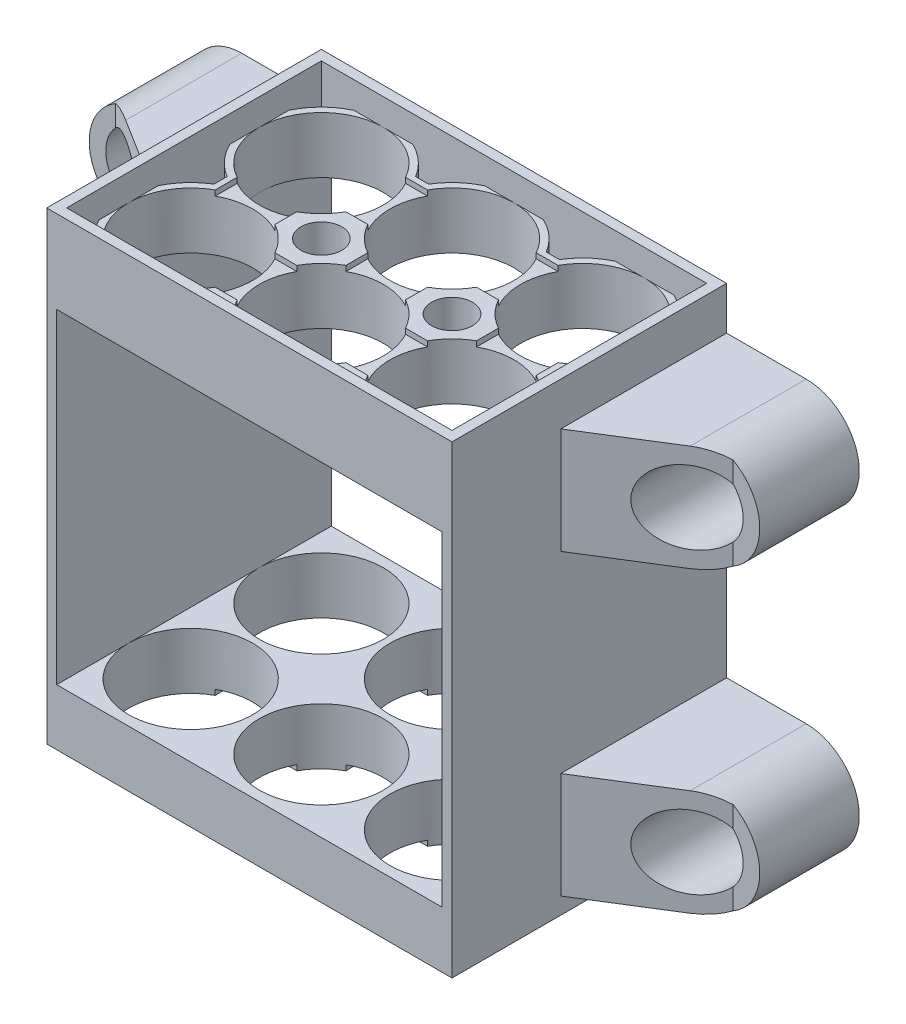
SolidWorks part; units mm, degrees
note: The reader was unsure of these and kept them because the rebuilt part matched: shared geometry of "Sketch5<3>", "Sketch12<3>".
ref_plane "Front Plane" through (0, 0, 0) normal (0, 0, 1) x (1, 0, 0)
ref_plane "Top Plane" through (0, 0, 0) normal (0, 1, 0) x (1, 0, 0)
ref_plane "Right Plane" through (0, 0, 0) normal (1, 0, 0) x (0, 0, -1)
sketch "Sketch3" plane through (0, 0, 0) normal (0, 1, 0) x (1, 0, 0)
  line L0 (-19.7, 9.85) -> (-10.35, 9.85) construction
  line L1 (-10.35, 9.85) -> (-9.35, 9.85) construction
  line L2 (-9.35, 9.85) -> (0, 9.85) construction
  line L3 (0, 9.85) -> (9.35, 9.85) construction
  line L4 (9.35, 9.85) -> (10.35, 9.85) construction
  line L5 (10.35, 9.85) -> (19.7, 9.85) construction
  line L6 (19.7, 9.85) -> (19.7, 0.5) construction
  line L7 (19.7, 0.5) -> (19.7, -0.5) construction
  line L8 (19.7, -0.5) -> (19.7, -9.85) construction
  line L9 (19.7, -9.85) -> (10.35, -9.85) construction
  line L10 (10.35, -9.85) -> (9.35, -9.85) construction
  line L11 (9.35, -9.85) -> (0, -9.85) construction
  line L12 (0, -9.85) -> (-9.35, -9.85) construction
  line L13 (-9.35, -9.85) -> (-10.35, -9.85) construction
  line L14 (-10.35, -9.85) -> (-19.7, -9.85) construction
  line L15 (-19.7, -9.85) -> (-19.7, -0.5) construction
  line L16 (-19.7, -0.5) -> (-19.7, 0.5) construction
  line L17 (-19.7, 0.5) -> (-19.7, 9.85) construction
  line L18 (0, 9.85) -> (0, 0.5) construction
  line L19 (0, 0.5) -> (0, -0.5) construction
  line L20 (0, -0.5) -> (0, -9.85) construction
  line L21 (0, 9.85) -> (0, 19.2) construction
  line L22 (-30.55, 20.7) -> (30.55, 20.7)
  line L23 (-30.55, 20.7) -> (-30.55, -20.7)
  line L24 (-30.55, -20.7) -> (30.55, -20.7)
  line L25 (30.55, 20.7) -> (30.55, -20.7)
  line L26 (0, 19.2) -> (0, 20.7) construction
  line L27 (-19.7, -9.85) -> (-29.05, -9.85) construction
  line L28 (-29.05, -9.85) -> (-30.55, -9.85) construction
  line L29 (-30.55, 20.7) -> (30.55, -20.7) construction
  circle A0 centre (-19.7, 9.85) radius 9.35
  circle A1 centre (0, 9.85) radius 9.35
  circle A2 centre (19.7, 9.85) radius 9.35
  circle A3 centre (-19.7, -9.85) radius 9.35
  circle A4 centre (0, -9.85) radius 9.35
  circle A5 centre (19.7, -9.85) radius 9.35
  dimension "D1" = 18.7
  dimension "D2" = 1
  dimension "D3" = 1
  dimension "D4" = 1
  dimension "D5" = 1.5
  dimension "D6" = 1.5
extrude "Boss-Extrude1" add sketch "Sketch3" along normal blind 66
sketch "Sketch4" plane through (0, 0, 0) normal (0, 1, 0) x (1, 0, 0)
  line L0 (-9.85, 0) -> (9.85, 0) construction
  line L1 (-19.7, -9.85) -> (0, 9.85) construction
  line L2 (-15.2615, 19.2) -> (-4.4385, 19.2)
  line L4 (-8.86, 15.2) -> (-10.84, 15.2)
  line L6 (-9.85, 19.2) -> (-9.85, 15.2) construction
  line L7 (-9.85, 0) -> (-9.85, 15.2) construction
  line L8 (-9.85, 19.2) -> (-9.85, 20.7) construction
  line L9 (30.55, 20.7) -> (-30.55, 20.7) construction
  line L10 (-9.85, 0) -> (-12.0279, 2.1779) construction
  line L11 (-12.0279, 2.1779) -> (-12.3814, 2.5314) construction
  line L12 (-12.3814, 2.5314) -> (-19.7, 9.85) construction
  line L13 (-4.4385, 19.2) -> (4.4385, 19.2) construction
  line L14 (4.4385, 19.2) -> (15.2615, 19.2)
  line L15 (15.2615, 19.2) -> (24.1385, 19.2) construction
  line L16 (24.1385, 19.2) -> (29.05, 19.2)
  line L17 (29.05, 19.2) -> (29.05, 14.2885)
  line L18 (29.05, 5.4115) -> (29.05, -5.4115)
  line L19 (29.05, -19.2) -> (29.05, -14.2885)
  line L20 (29.05, -19.2) -> (24.1385, -19.2)
  line L21 (24.1385, -19.2) -> (15.2615, -19.2) construction
  line L22 (15.2615, -19.2) -> (4.4385, -19.2)
  line L23 (4.4385, -19.2) -> (-4.4385, -19.2) construction
  line L24 (-4.4385, -19.2) -> (-15.2615, -19.2)
  line L25 (-15.2615, -19.2) -> (-24.1385, -19.2) construction
  line L26 (-24.1385, -19.2) -> (-29.05, -19.2)
  line L27 (-29.05, -19.2) -> (-29.05, -14.2885)
  line L28 (-29.05, -14.2885) -> (-29.05, -5.4115) construction
  line L29 (-29.05, -5.4115) -> (-29.05, 5.4115)
  line L30 (-29.05, 5.4115) -> (-29.05, 14.2885) construction
  line L31 (-29.05, 14.2885) -> (-29.05, 19.2)
  line L32 (-29.05, 19.2) -> (-24.1385, 19.2)
  line L33 (-24.1385, 19.2) -> (-15.2615, 19.2) construction
  line L34 (-30.55, 20.7) -> (-30.55, -20.7) construction
  line L35 (30.55, -20.7) -> (30.55, 20.7) construction
  line L36 (-30.55, -20.7) -> (30.55, -20.7) construction
  line L37 (29.05, 14.2885) -> (29.05, 5.4115) construction
  line L38 (29.05, -14.2885) -> (29.05, -5.4115) construction
  line L39 (8.86, 15.2) -> (10.84, 15.2)
  line L40 (25.05, 0.99) -> (25.05, -0.99)
  line L41 (0, -20.2) -> (19.7, -20.2)
  line L42 (10.84, -15.2) -> (8.86, -15.2)
  line L43 (-8.86, -15.2) -> (-10.84, -15.2)
  line L44 (-30.05, 9.85) -> (-30.05, -9.85)
  line L45 (-25.05, 0.99) -> (-25.05, -0.99)
  circle A0 centre (-9.85, 0) radius 3.08
  circle A1 centre (9.85, 0) radius 3.08
  circle A2 centre (-19.7, 9.85) radius 10.35
  circle A3 centre (-19.7, 9.85) radius 9.35 construction
  circle A4 centre (0, 9.85) radius 10.35
  circle A5 centre (19.7, 9.85) radius 10.35
  circle A6 centre (19.7, -9.85) radius 10.35
  circle A7 centre (0, -9.85) radius 10.35
  circle A8 centre (-19.7, -9.85) radius 10.35
  dimension "D1" = 0.5
  dimension "D2" = 1
  dimension "D3" = 4
  dimension "D4" = 1.5
  dimension "D5" = 1.5
  dimension "D6" = 1.5
  dimension "D7" = 1.5
  dimension "D8" = 4
  dimension "D9" = 4
  dimension "D10" = 4
  dimension "D11" = 4
  dimension "D12" = 4
extrude "Cut-Extrude1" cut sketch "Sketch4" along normal through all contours A0 | A1 | A4 L2 A2 L4 | A5 L14 A4 L39 | A6 L18 A5 L40 | A6 L20 L19 | A5 L17 L16 | A7 L22 A6 L42 | A8 L24 A7 L43 | A8 L27 L26 | A8 L45 A2 L29 | A2 L32 L31
sketch "Sketch5" plane through (0, 0, 0) normal (0, 0, 1) x (1, 0, 0)
  line L0 (-30.55, 66) -> (-30.55, 0) construction
  line L1 (-30.55, 57.5) -> (30.55, 57.5)
  line L2 (-30.55, 57.5) -> (-30.55, 8.5)
  line L3 (-30.55, 8.5) -> (30.55, 8.5)
  line L4 (30.55, 57.5) -> (30.55, 8.5)
  line L5 (30.55, 66) -> (30.55, 0) construction
  line L6 (0, 0) -> (0, 8.5) construction
  line L7 (0, 8.5) -> (0, 57.5) construction
  line L8 (0, 57.5) -> (0, 66) construction
  line L9 (-30.55, 66) -> (30.55, 66) construction
  line L10 (-29.05, 57.5) -> (-29.05, 8.5)
  line L11 (-30.55, 57.5) -> (30.55, 57.5)
  line L12 (-30.55, 57.5) -> (-30.55, 58.5)
  line L13 (-30.55, 58.5) -> (30.55, 58.5)
  line L14 (30.55, 57.5) -> (30.55, 58.5)
  line L15 (-30.55, 8.5) -> (30.55, 8.5)
  line L16 (-30.55, 8.5) -> (-30.55, 7.5)
  line L17 (-30.55, 7.5) -> (30.55, 7.5)
  line L18 (30.55, 8.5) -> (30.55, 7.5)
  line L19 (29.05, 57.5) -> (29.05, 8.5)
  dimension "D1" = 8.5
  dimension "D2" = 1
  dimension "D3" = 1.5
  dimension "D4" = 1.5
extrude "Boss-Extrude2" add sketch "Sketch5" along normal up to surface and the other way up to surface contours L1 L14 L13 L12 | L18 L3 L16 L17 up to face at (0, 33, 20.7) other way up to face at (0, 33, -20.7)
extrude "Cut-Extrude3" cut sketch "Sketch5<3>" against normal through all both and the other way through all contours L4 L1 L2 L3
sketch "Sketch5<3>" plane through (0, 0, 0) normal (0, 0, 1) x (1, 0, 0) same geometry as "Sketch5"
sketch "Sketch7" plane through (0, 0, 0) normal (0, 1, 0) x (1, 0, 0)
  circle A0 centre (-19.7, 9.85) radius 9.35
  circle A1 centre (0, 9.85) radius 9.35
  circle A2 centre (19.7, 9.85) radius 9.35
  circle A3 centre (19.7, -9.85) radius 9.35
  circle A4 centre (0, -9.85) radius 9.35
  circle A5 centre (-19.7, -9.85) radius 9.35
  circle A6 centre (-19.7, -9.85) radius 9.35 construction
  circle A7 centre (0, 9.85) radius 9.35 construction
  circle A8 centre (-19.7, 9.85) radius 9.35 construction
  circle A9 centre (19.7, 9.85) radius 9.35 construction
  circle A10 centre (19.7, -9.85) radius 9.35 construction
  circle A11 centre (0, -9.85) radius 9.35 construction
extrude "Cut-Extrude4" cut sketch "Sketch7" along normal through all
sketch "Sketch8" plane through (0, 0, 0) normal (0, 0, 1) x (1, 0, 0)
  line L0 (-42.55, 55.5) -> (-42.55, 10.5) construction
  line L1 (-42.55, 10.5) -> (42.55, 10.5) construction
  line L2 (42.55, 10.5) -> (42.55, 55.5) construction
  line L3 (42.55, 55.5) -> (-42.55, 55.5) construction
  line L4 (0, 55.5) -> (0, 10.5) construction
  line L5 (-29.05, 8.5) -> (29.05, 57.5) construction
  line L6 (-42.55, 63.5) -> (-30.55, 63.5)
  line L7 (-30.55, 66) -> (-30.55, 0) construction
  line L8 (-30.55, 63.5) -> (-30.55, 47.5)
  line L9 (-30.55, 47.5) -> (-42.55, 47.5)
  line L10 (-42.55, 18.5) -> (-30.55, 18.5)
  line L11 (-42.55, 2.5) -> (-30.55, 2.5)
  line L12 (-30.55, 2.5) -> (-30.55, 18.5)
  line L13 (42.55, 2.5) -> (30.55, 2.5)
  line L14 (30.55, 66) -> (30.55, 0) construction
  line L15 (42.55, 18.5) -> (30.55, 18.5)
  line L16 (30.55, 18.5) -> (30.55, 2.5)
  line L17 (42.55, 47.5) -> (30.55, 47.5)
  line L18 (42.55, 63.5) -> (30.55, 63.5)
  line L19 (30.55, 63.5) -> (30.55, 47.5)
  line L20 (50.55, 55.5) -> (50.55, 10.5) construction
  line L21 (50.55, 33) -> (30.55, 33) construction
  circle A0 centre (-42.55, 55.5) radius 5.5
  circle A1 centre (-42.55, 10.5) radius 5.5
  circle A2 centre (42.55, 10.5) radius 5.5
  circle A3 centre (42.55, 55.5) radius 5.5
  circle A4 centre (-42.55, 55.5) radius 8
  circle A5 centre (-42.55, 10.5) radius 8
  circle A6 centre (42.55, 10.5) radius 8
  circle A7 centre (42.55, 55.5) radius 8
  point P14 (0, 33)
  dimension "D1" = 2.5
  dimension "D2" = 16
  dimension "D3" = 45
  dimension "D4" = 20
extrude "Boss-Extrude3" add sketch "Sketch8" along normal up to surface and the other way up to surface contours A4 L9 L8 L6 | A4 A0 | A7 L18 L19 L17 | A7 A3 | A6 L15 L16 L13 | A6 A2 | A5 A1 | A5 L11 L12 L10
sketch "Sketch9" plane through (0, 0, 0) normal (0, 1, 0) x (1, 0, 0)
  line L0 (-30.55, 20.7) -> (-50.55, 20.7)
  line L1 (-50.55, 20.7) -> (-50.55, 5.7)
  line L2 (-50.55, 20.7) -> (-50.55, -20.7) construction
  line L3 (-50.55, 5.7) -> (-46.55, 5.7)
  line L4 (-46.55, 5.7) -> (-30.55, -4.3)
  line L5 (-30.55, -20.7) -> (-30.55, 20.7) construction
  line L6 (-30.55, -4.3) -> (-30.55, 20.7)
  line L7 (-30.55, -4.3) -> (30.55, -4.3) construction
  line L8 (30.55, -20.7) -> (30.55, 20.7) construction
  line L9 (30.55, -4.3) -> (30.55, 20.7)
  line L10 (30.55, 20.7) -> (42.55, 20.7) construction
  line L11 (30.55, -4.3) -> (46.55, 5.7)
  line L12 (46.55, 5.7) -> (50.55, 5.7)
  line L13 (50.55, -20.7) -> (50.55, 20.7) construction
  line L14 (50.55, 5.7) -> (50.55, 20.7)
  line L15 (50.55, 20.7) -> (30.55, 20.7)
  line L16 (-50.55, 5.7) -> (-50.55, -20.7)
  line L17 (-50.55, -20.7) -> (-30.55, -20.7)
  line L18 (-30.55, -20.7) -> (-30.55, -4.3)
  line L19 (50.55, 5.7) -> (50.55, -20.7)
  line L20 (50.55, -20.7) -> (30.55, -20.7)
  line L21 (30.55, -20.7) -> (30.55, -4.3)
  dimension "D1" = 4
  dimension "D2" = 15
  dimension "D3" = 25
extrude "Cut-Extrude6" cut sketch "Sketch9" against normal through all and the other way through all contours L17 L18 L4 L3 L16 | L21 L20 L19 L12 L11
sketch "Sketch10" plane through (0, 0, -20.7) normal (0, 0, -1) x (-1, 0, 0)
  circle A0 centre (42.55, 10.5) radius 2.25
  circle A1 centre (42.55, 10.5) radius 8
  circle A2 centre (42.55, 55.5) radius 2.25
  circle A3 centre (42.55, 55.5) radius 8
  circle A4 centre (-42.55, 55.5) radius 8
  circle A5 centre (-42.55, 55.5) radius 2.25
  circle A6 centre (-42.55, 10.5) radius 2.25
  circle A7 centre (-42.55, 10.5) radius 8
  arc A8 (-42.55, 18.5) -> (-42.55, 2.5) centre (-42.55, 10.5) ccw construction
  arc A9 (42.55, 2.5) -> (42.55, 18.5) centre (42.55, 10.5) ccw construction
  arc A10 (42.55, 47.5) -> (42.55, 63.5) centre (42.55, 55.5) ccw construction
  arc A11 (-42.55, 63.5) -> (-42.55, 47.5) centre (-42.55, 55.5) ccw construction
  dimension "D1" = 4.5
extrude "Boss-Extrude4" add sketch "Sketch10" against normal blind 5
sketch "Sketch11" plane through (0, 66, 0) normal (0, 1, 0) x (1, 0, 0)
  line L1 (-30.55, 20.7) -> (30.55, 20.7)
  line L2 (-30.55, 20.7) -> (-30.55, -20.7)
  line L3 (-30.55, -20.7) -> (30.55, -20.7)
  line L4 (30.55, 20.7) -> (30.55, -20.7)
  line L5 (-29.05, 19.2) -> (29.05, 19.2)
  line L6 (-29.05, 19.2) -> (-29.05, -19.2)
  line L7 (-29.05, -19.2) -> (29.05, -19.2)
  line L8 (29.05, 19.2) -> (29.05, -19.2)
extrude "Boss-Extrude5" add sketch "Sketch11" along normal blind 4
sketch "Sketch12" plane through (0, 66, 0) normal (0, 1, 0) x (1, 0, 0)
  line L0 (-24.2, -14.35) -> (24.2, -14.35)
  line L9 (24.2, -14.35) -> (24.2, 14.35)
  line L10 (24.2, 14.35) -> (-24.2, 14.35)
  line L11 (-24.2, 14.35) -> (-24.2, -14.35)
  line L12 (-15.2, -5.35) -> (-4.5, -5.35)
  line L13 (-4.5, -5.35) -> (-4.5, 5.35)
  line L14 (-4.5, 5.35) -> (-15.2, 5.35)
  line L15 (-15.2, 5.35) -> (-15.2, -5.35)
  line L16 (15.2, -5.35) -> (4.5, -5.35)
  line L17 (4.5, -5.35) -> (4.5, 5.35)
  line L18 (4.5, 5.35) -> (15.2, 5.35)
  line L19 (15.2, 5.35) -> (15.2, -5.35)
  line L20 (4.5, -5.35) -> (-4.5, -5.35) construction
  line L21 (4.5, 5.35) -> (-4.5, 5.35) construction
  line L22 (0, 0) -> (0, -5.35) construction
  line L23 (0, 0) -> (-4.5, 0) construction
  line L24 (24.2, 0) -> (15.2, 0)
  line L25 (-9.85, -5.35) -> (-9.85, -14.35) construction
  line L26 (-9.85, -9.85) -> (-19.7, -9.85) construction
  line L27 (-15.2, 0) -> (-24.2, 0) construction
  line L28 (-19.7, -9.85) -> (-19.7, 0) construction
  point P26 (-4.9886, 5.35)
  arc M21 (-29.05, -9.85) -> (-19.7, -19.2) centre (-19.7, -9.85) cw
  circle M27 centre (0, -9.85) radius 9.35
  arc M33 (19.7, -19.2) -> (29.05, -9.85) centre (19.7, -9.85) cw
  arc M39 (29.05, 9.85) -> (19.7, 19.2) centre (19.7, 9.85) cw
  circle M45 centre (0, 9.85) radius 9.35
  arc M51 (-19.7, 19.2) -> (-29.05, 9.85) centre (-19.7, 9.85) cw
  dimension "D1" = 9
  dimension "D2" = 9
  dimension "D3" = 9
  dimension "D4" = 9
extrude "Cut-Extrude7" cut sketch "Sketch12" against normal blind 0.8 contours L15 L14 L10 L11 M51 | L15 L11 L0 L12 M21 | L12 L0 M21 M27 | L16 L17 L13 L12 L0 M27 | L17 L18 L10 L14 L13 M45 | L14 L10 M45 M51 | L17 L13 M27 M45 | L19 L16 L0 L9 M33 | L18 L19 L9 L10 M39 | L24 L9 L19 M39 | L9 L24 L19 M33 | L16 L0 M33 M27 | L18 L10 M45 M39 | L15 L11 M51 M21
extrude "Cut-Extrude8" cut sketch "Sketch12<3>" along normal blind 0.8 from surface at -66 contours L15 L14 L10 L11 M51 | L15 L11 L0 L12 M21 | L15 L11 M51 M21 | L12 L0 M21 M27 | L14 L10 M45 M51 | L17 L18 L10 L14 L13 M45 | L16 L17 L13 L12 L0 M27 | L17 L13 M27 M45 | L19 L16 L0 L9 M33 | L18 L19 L9 L10 M39 | L18 L10 M45 M39 | L16 L0 M33 M27 | L9 L24 L19 M33 | L24 L9 L19 M39 starting at face at (9.85, 0, 3.08)
sketch "Sketch12<3>" plane through (0, 66, 0) normal (0, 1, 0) x (1, 0, 0) same geometry as "Sketch12"
